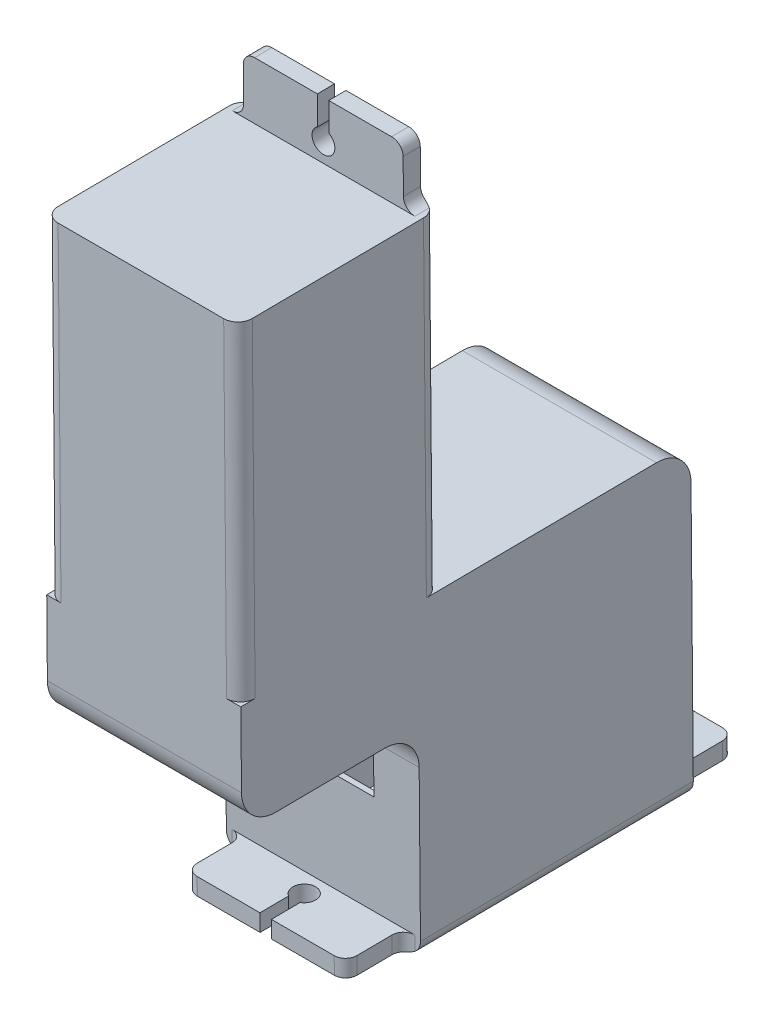
SolidWorks part; units mm, degrees
ref_plane "Front Plane" through (0, 0, 0) normal (0, 0, 1) x (1, 0, 0)
ref_plane "Top Plane" through (0, 0, 0) normal (0, 1, 0) x (1, 0, 0)
ref_plane "Right Plane" through (0, 0, 0) normal (1, 0, 0) x (0, 0, -1)
sketch "Sketch2" plane through (0, 48.5549, 0.4237) normal (0, 1, 0.0087) x (1, 0, 0)
  line L0 (-9.0464, 2.1053) -> (-9.0464, -2.2447) construction
  line L1 (-8.0464, -3.4447) -> (-22.0464, -3.4447)
  line L2 (-8.0464, -3.4447) -> (-8.0464, 2.1092)
  line L3 (-8.0464, 2.1092) -> (-22.0464, 2.1092)
  line L4 (-22.0464, -3.4447) -> (-22.0464, 2.1092)
  line L5 (-21.0464, -2.2447) -> (-21.0464, 2.1053) construction
  line L6 (-15.5464, -2.4447) -> (-20.8464, -2.4447) construction
  dimension "D1" = 1
  dimension "D2" = 1
  dimension "D3" = 1
extrude "Boss-Extrude1" add sketch "Sketch2" along normal blind 1.5
sketch "Sketch3" plane through (0, 48.5549, 0.4237) normal (0, -1, -0.0087) x (1, 0, 0)
  line L0 (-16.0464, 0.0697) -> (-14.0464, 0.0697) construction
  line L1 (-15.5464, 0.9358) -> (-15.5464, 3.4447)
  line L2 (-22.0464, 3.4447) -> (-8.0464, 3.4447) construction
  line L3 (-14.5464, 0.9358) -> (-14.5464, 2.4447)
  line L4 (-14.5464, 2.4447) -> (-14.5464, 3.4447)
  line L5 (-14.5464, 3.4447) -> (-15.5464, 3.4447)
  arc A0 (-15.5464, 0.9358) -> (-14.5464, 0.9358) centre (-15.0464, 0.0697) ccw construction
  circle A1 centre (-15.0464, 0.0697) radius 1
  line M2 (-8.0464, 3.4447) -> (-22.0464, 3.4447)
extrude "Cut-Extrude1" cut sketch "Sketch3" against normal up to next contours A1 L0 | A1 L3 L4 L1 M2
sketch "Sketch4" plane through (0, 50.0548, 0.4368) normal (0, 1, 0.0087) x (1, 0, 0)
  line L0 (-20.8464, 24.6053) -> (-20.8464, 2.5053) construction
  line L1 (-20.8464, 13.5553) -> (-23.5464, 13.5553)
  line L2 (-21.0464, 2.5053) -> (-21.0464, 24.6053) construction
  line L3 (-23.5464, 2.1092) -> (-23.5464, 13.5553)
  line L4 (-22.0464, -3.4447) -> (-23.1358, -3.4447)
  line L5 (-21.5464, 2.1092) -> (-21.5464, 13.5553)
  line L6 (-23.5464, 13.5553) -> (-23.5464, 15.5553)
  line L7 (-23.5464, 15.5553) -> (-21.5464, 15.5553)
  line L8 (-23.5464, 2.1092) -> (-23.5464, -3.4447)
  line L9 (-23.5464, -3.4447) -> (-23.1358, -3.4447)
  line L10 (-21.5464, 2.1092) -> (-22.0464, 2.1092)
  line L11 (-22.0464, 2.1092) -> (-22.0464, -3.4447)
  line L12 (-15.0464, 0.9303) -> (-15.0464, 3.2859)
  line L13 (-9.2464, 13.5553) -> (-6.5464, 13.5553)
  line L14 (-8.5464, 2.1092) -> (-8.5464, 13.5553)
  line L15 (-8.5464, 2.1092) -> (-8.0464, 2.1092)
  line L16 (-8.0464, 2.1092) -> (-8.0464, -3.4447)
  line L17 (-8.0464, -3.4447) -> (-6.957, -3.4447)
  line L18 (-6.5464, -3.4447) -> (-6.957, -3.4447)
  line L19 (-6.5464, 2.1092) -> (-6.5464, -3.4447)
  line L20 (-6.5464, 2.1092) -> (-6.5464, 13.5553)
  line L21 (-21.5464, 2.1092) -> (-21.5464, -3.4447)
  line L22 (-22.0464, -3.4447) -> (-15.5464, -3.4447) construction
  line L23 (-21.5464, -3.4447) -> (-22.0464, -3.4447)
  line L24 (-8.0464, -3.4447) -> (-8.5464, -3.4447)
  line L25 (-14.5464, -3.4447) -> (-8.0464, -3.4447) construction
  line L26 (-8.5464, -3.4447) -> (-8.5464, 2.1092)
  line L27 (-21.5464, 2.1092) -> (-8.5464, 2.1092)
  line L28 (-6.5464, 1.6092) -> (-23.5464, 1.6092)
  line L29 (-21.5464, 15.5553) -> (-21.5464, 13.5553)
  line L30 (-8.5464, 13.5553) -> (-8.5464, 15.5553)
  line L31 (-8.5464, 15.5553) -> (-6.5464, 15.5553)
  line L32 (-6.5464, 15.5553) -> (-6.5464, 13.5553)
  arc A0 (-14.5464, -0.9358) -> (-15.5464, -0.9358) centre (-15.0464, -0.0697) ccw construction
  line M13 (-8.0464, 2.1092) -> (-22.0464, 2.1092)
  line M14 (-22.0464, 2.1092) -> (-22.0464, -3.4447)
  dimension "D1" = 0.5
  dimension "D2" = 2
  dimension "D3" = 0.5
  dimension "D4" = 2
extrude "Boss-Extrude2" add sketch "Sketch4" along normal blind 16 and the other way up to surface contours L28 L12 L21 M13 | L28 L26 L12 M13 | L28 L16 L26 M13 | L28 L19 L20 L13 L14 L16 M13 | L28 L5 L1 L3 L8 M14 M13 | L28 L21 M13 M14
fillet "Fillet1" radius 1 4 edges at (-8.0464, 49.2748, 3.8749) (-22.0464, 49.2748, 3.8749) (-22.0464, 49.3189, -1.1788) (-8.0464, 49.3189, -1.1788)
sketch "Sketch5" plane through (0, 0.0184, -2.1091) normal (0, 0.0087, -1) x (-1, 0, 0)
  line L0 (21.5464, 48.5567) -> (21.5464, 66.0567) construction
  line L1 (8.5464, 66.0567) -> (21.5464, 66.0567)
  line L2 (8.5464, 66.0567) -> (8.5464, 64.7567)
  line L3 (8.5464, 64.7567) -> (21.5464, 64.7567)
  line L4 (21.5464, 66.0567) -> (21.5464, 64.7567)
  line L5 (9.2464, 64.5567) -> (20.8464, 64.5567) construction
  dimension "D1" = 0.2
extrude "Boss-Extrude3" add sketch "Sketch5" along normal up to surface (11.4461 mm away) up to face at (-7.5464, 57.4228, -13.0547)
fillet "Fillet2" radius 1.25 4 edges at (-6.5464, 48.621, -7.1582) (-6.5464, 66.1204, -7.0055) (-23.5464, 48.621, -7.1582) (-23.5464, 66.1204, -7.0055)
mirror "Mirror1" about plane through (0, 27.8963, -13.3123) normal (0, -0.0087, 1) of bodies 104
sketch "Sketch10" plane through (0, 0.014, -1.6091) normal (0, -0.0087, 1) x (1, 0, 0)
  line L0 (-15.0464, 66.0567) -> (-15.0464, 62.8067)
  line L1 (-7.7964, 66.0567) -> (-22.2964, 66.0567) construction
  line L3 (-15.0464, 62.8067) -> (-10.5464, 62.8067)
  line L4 (-10.5464, 62.8067) -> (-10.5464, 58.8067)
  line L5 (-10.5464, 58.8067) -> (-19.5464, 58.8067)
  line L6 (-19.5464, 58.8067) -> (-19.5464, 62.8067)
  line L7 (-19.5464, 62.8067) -> (-15.0464, 62.8067)
  dimension "D1" = 3.25
  dimension "D2" = 9
  dimension "D3" = 4.5
  dimension "D4" = 4
extrude "Cut-Extrude2" cut sketch "Sketch10" against normal blind 5 contours L7 L6 L5 L4 L3
sketch "Sketch11" plane through (-10.5464, 0, 0) normal (-1, 0, 0) x (0, 0, 1)
  line L0 (-1.0959, 58.8185) -> (-1.5959, 58.8229)
  line L1 (-1.5959, 58.8229) -> (-1.6892, 48.1333)
  line L2 (-1.6892, 48.1333) -> (-1.1892, 48.1333)
  line L3 (-1.1892, 48.1333) -> (-1.5959, 58.8229)
  dimension "D1" = 0.5
ref_plane "Plane2" through (0, -0.1173, 13.4442) normal (0, -0.0087, 1) x (1, 0, 0)
sketch "Sketch14" plane through (0, -0.1173, 13.4442) normal (0, -0.0087, 1) x (1, 0, 0)
  line L0 (-8.7473, 50.1358) -> (-14.839, 48.49)
  line L1 (-8.7473, 50.1358) -> (-6.5464, 52.3367)
  line L2 (-6.5464, 49.8067) -> (-6.5464, 64.8067) construction
  line L3 (-6.5464, 52.3367) -> (-6.5464, 71.0567)
  line L4 (-6.5464, 71.0567) -> (-16.7045, 71.0567)
  line L5 (-7.7964, 66.0567) -> (-22.2964, 66.0567) construction
  line L6 (-14.839, 48.49) -> (8.8302, 48.49)
  line L7 (0, 65.6042) -> (-11.5834, 65.6042)
  line L8 (0, 19.4955) -> (0, -19.4955) construction
  dimension "D1" = 5
pattern_circular "CirPattern1" count 2 over 360 about axis through (0, 65.4843, 14.0167) along (-1, 0, 0)
sketch "Sketch15" plane through (0, 66.0542, 0.5764) normal (0, 1, 0.0087) x (1, 0, 0)
  line L0 (-7.7964, 25.5014) -> (-7.7964, -15.9286)
  line L1 (-7.7964, -15.9286) -> (-22.2964, -15.9286)
  line L2 (-22.2964, -15.9286) -> (-22.2964, 25.5014)
  line L3 (-22.2964, 25.5014) -> (-7.7964, 25.5014)
extrude "Boss-Extrude4" add sketch "Sketch15" along normal up to surface (9.5475 mm away) up to face at (-18.2964, 75.6262, -2.1929)
sketch "Sketch16" plane through (0, 80.655, 0.7039) normal (0, -1, -0.0087) x (1, 0, 0)
  line L6 (-23.0464, -2.1027) -> (-21.8589, -2.1027)
  line L12 (-7.0464, -2.1027) -> (-7.0464, -3.3527)
  line L13 (-6.5464, -2.3527) -> (-6.5464, 12.6473)
  line L14 (-7.7964, 13.8973) -> (-22.2964, 13.8973)
  line L15 (-23.5464, 12.6473) -> (-23.5464, -2.3527)
  line L16 (-23.0464, -3.3527) -> (-23.0464, -2.1027)
  line L17 (-23.0464, -2.1027) -> (-7.0464, -2.1027)
  line L18 (-7.0464, -2.1027) -> (-7.0464, -3.3527)
  line L19 (-6.5464, -2.3527) -> (-6.5464, 12.6473)
  line L20 (-7.7964, 13.8973) -> (-22.2964, 13.8973)
  line L21 (-23.5464, 12.6473) -> (-23.5464, -2.3527)
  line L22 (-23.0464, -3.3527) -> (-23.0464, -2.1027)
  line L23 (-23.0464, -2.1027) -> (-7.0464, -2.1027)
  line L27 (-8.0464, -3.6027) -> (-7.7964, -3.6027)
  line L28 (-7.0464, -3.3527) -> (-7.0464, -2.1027)
  line L29 (-7.0464, -2.1027) -> (-8.0464, -2.1027)
  line L30 (-8.0464, -2.1027) -> (-8.0464, -3.6027)
  line L31 (-8.0464, -3.6027) -> (-7.7964, -3.6027)
  line L32 (-7.0464, -3.3527) -> (-7.0464, -2.1027)
  line L33 (-7.0464, -2.1027) -> (-8.0464, -2.1027)
  line L34 (-8.0464, -2.1027) -> (-8.0464, -3.6027)
  line L35 (-23.0464, -2.1027) -> (-22.0464, -2.1027)
  line L36 (-22.0464, -2.1027) -> (-22.0464, -3.6027)
  line L37 (-23.0464, -3.3527) -> (-23.0464, -2.1027)
  line L39 (-23.0464, -2.1027) -> (-23.0464, -3.3527)
  line L40 (-22.2964, -3.6027) -> (-22.0464, -3.6027)
  line L41 (-22.0464, -3.6027) -> (-22.0464, -2.1027)
  line L42 (-22.0464, -2.1027) -> (-23.0464, -2.1027)
  line L43 (-23.0464, -2.1027) -> (-23.0464, -3.3527)
  line L44 (-22.2964, -3.6027) -> (-22.0464, -3.6027)
  line L45 (-22.0464, -3.6027) -> (-22.0464, -2.1027)
  line L46 (-22.0464, -2.1027) -> (-23.0464, -2.1027)
  arc A6 (-7.7964, -3.6027) -> (-7.0464, -3.3527) centre (-7.7964, -2.3527) ccw
  arc A7 (-7.7964, -3.6027) -> (-7.0464, -3.3527) centre (-7.7964, -2.3527) ccw
  arc A8 (-7.0464, -3.3527) -> (-6.5464, -2.3527) centre (-7.7964, -2.3527) ccw
  arc A9 (-6.5464, 12.6473) -> (-7.7964, 13.8973) centre (-7.7964, 12.6473) ccw
  arc A10 (-22.2964, 13.8973) -> (-23.5464, 12.6473) centre (-22.2964, 12.6473) ccw
  arc A11 (-23.5464, -2.3527) -> (-23.0464, -3.3527) centre (-22.2964, -2.3527) ccw
  arc A12 (-7.0464, -3.3527) -> (-6.5464, -2.3527) centre (-7.7964, -2.3527) ccw
  arc A13 (-6.5464, 12.6473) -> (-7.7964, 13.8973) centre (-7.7964, 12.6473) ccw
  arc A14 (-22.2964, 13.8973) -> (-23.5464, 12.6473) centre (-22.2964, 12.6473) ccw
  arc A15 (-23.5464, -2.3527) -> (-23.0464, -3.3527) centre (-22.2964, -2.3527) ccw
  arc A16 (-22.0464, -3.6027) -> (-23.0464, -3.3527) centre (-22.0464, -1.4777) cw
  arc A17 (-23.0464, -3.3527) -> (-22.2964, -3.6027) centre (-22.2964, -2.3527) ccw
  arc A18 (-23.0464, -3.3527) -> (-22.2964, -3.6027) centre (-22.2964, -2.3527) ccw
  line M11 (-7.0464, -2.1027) -> (-7.0464, -3.3527)
  arc M12 (-7.0464, -3.3527) -> (-6.5464, -2.3527) centre (-7.7964, -2.3527) ccw
  line M13 (-6.5464, -2.3527) -> (-6.5464, 12.6473)
  arc M14 (-6.5464, 12.6473) -> (-7.7964, 13.8973) centre (-7.7964, 12.6473) ccw
  line M15 (-7.7964, 13.8973) -> (-22.2964, 13.8973)
  arc M16 (-22.2964, 13.8973) -> (-23.5464, 12.6473) centre (-22.2964, 12.6473) ccw
  line M17 (-23.5464, 12.6473) -> (-23.5464, -2.3527)
  arc M18 (-23.5464, -2.3527) -> (-23.0464, -3.3527) centre (-22.2964, -2.3527) ccw
  line M19 (-23.0464, -3.3527) -> (-23.0464, -2.1027)
  line M20 (-23.0464, -2.1027) -> (-7.0464, -2.1027)
  line M21 (-19.5464, 10.6473) -> (-10.5464, 10.6473)
  line M22 (-10.5464, 10.6473) -> (-10.5464, 6.6473)
  line M23 (-10.5464, 6.6473) -> (-19.5464, 6.6473)
  line M24 (-19.5464, 6.6473) -> (-19.5464, 10.6473)
  dimension "D1" = 0
  dimension "D2" = 0
  dimension "D3" = 0
sketch "Sketch19" plane through (0, 80.655, 0.7039) normal (0, -1, -0.0087) x (1, 0, 0)
  line L6 (-7.0464, -2.1027) -> (-8.0464, -2.1027)
  line L7 (-8.0464, -2.1027) -> (-8.0464, -3.6027)
  line L12 (-7.0464, -2.1027) -> (-7.0464, -3.3527)
  line L13 (-6.5464, -2.3527) -> (-6.5464, 12.6473)
  line L14 (-7.7964, 13.8973) -> (-22.2964, 13.8973)
  line L15 (-23.5464, 12.6473) -> (-23.5464, -2.3527)
  line L16 (-23.0464, -3.3527) -> (-23.0464, -2.1027)
  line L17 (-23.0464, -2.1027) -> (-7.0464, -2.1027)
  line L18 (-7.0464, -2.1027) -> (-7.0464, -3.3527)
  line L19 (-6.5464, -2.3527) -> (-6.5464, 12.6473)
  line L20 (-7.7964, 13.8973) -> (-22.2964, 13.8973)
  line L21 (-23.5464, 12.6473) -> (-23.5464, -2.3527)
  line L22 (-23.0464, -3.3527) -> (-23.0464, -2.1027)
  line L23 (-23.0464, -2.1027) -> (-7.0464, -2.1027)
  arc A4 (-8.0464, -3.6027) -> (-7.0464, -3.3527) centre (-8.0464, -1.4777) ccw
  arc A8 (-7.0464, -3.3527) -> (-6.5464, -2.3527) centre (-7.7964, -2.3527) ccw
  arc A9 (-6.5464, 12.6473) -> (-7.7964, 13.8973) centre (-7.7964, 12.6473) ccw
  arc A10 (-22.2964, 13.8973) -> (-23.5464, 12.6473) centre (-22.2964, 12.6473) ccw
  arc A11 (-23.5464, -2.3527) -> (-23.0464, -3.3527) centre (-22.2964, -2.3527) ccw
  arc A12 (-7.0464, -3.3527) -> (-6.5464, -2.3527) centre (-7.7964, -2.3527) ccw
  arc A13 (-6.5464, 12.6473) -> (-7.7964, 13.8973) centre (-7.7964, 12.6473) ccw
  arc A14 (-22.2964, 13.8973) -> (-23.5464, 12.6473) centre (-22.2964, 12.6473) ccw
  arc A15 (-23.5464, -2.3527) -> (-23.0464, -3.3527) centre (-22.2964, -2.3527) ccw
  point P9 (0, 0)
  dimension "D1" = 0
extrude "Boss-Extrude6" add sketch "Sketch16" along normal up to surface (5.0539 mm away) contours A16 L36 M20 M19 | L23 M20 M11 M12 M13 M14 M15 M16 M17 M18 M19 M24 M21 M22 M23 | L31 A7 L23 L34 M11
fillet "Fillet3" radius 1 2 edges at (-7.7964, 75.5564, 5.8068) (-22.2964, 75.5563, 5.8142)
sketch "Sketch20" plane through (0, 75.6013, 0.6598) normal (0, 1, 0.0087) x (1, 0, 0)
  line L8 (-7.7964, -15.9286) -> (-7.7964, -13.8973)
  line L9 (-7.7964, -13.8973) -> (-22.2964, -13.8973)
  line L10 (-22.2964, -13.8973) -> (-22.2964, -15.9286)
  line L11 (-22.2964, -15.9286) -> (-7.7964, -15.9286)
  line L12 (-7.7964, -15.9286) -> (-7.7964, -13.8973)
  line L13 (-7.7964, -13.8973) -> (-22.2964, -13.8973)
  line L14 (-22.2964, -13.8973) -> (-22.2964, -15.9286)
  line L15 (-22.2964, -15.9286) -> (-7.7964, -15.9286)
  dimension "D1" = 0
extrude "Cut-Extrude5" cut sketch "Sketch20" against normal up to surface (9.5475 mm away) up to face at (-15.0464, 65.9917, 7.7359)
fillet "Fillet4" radius 3 3 edges at (-15.0464, 65.9329, 14.4732) (-15.0464, 75.8238, -24.8406) (-15.0464, 66.0682, -1.0327)
sketch "Sketch21" plane through (0, 81.155, 0.7082) normal (0, 1, 0.0087) x (1, 0, 0)
  line L0 (-10.5464, -6.6473) -> (-10.5464, -10.6473)
  line L1 (-10.5464, -10.6473) -> (-19.5464, -10.6473)
  line L2 (-19.5464, -10.6473) -> (-19.5464, -6.6473)
  line L3 (-19.5464, -6.6473) -> (-10.5464, -6.6473)
extrude "Cut-Extrude6" cut sketch "Sketch21" against normal up to surface (15.1014 mm away) up to face at (-15.0464, 66.0006, 6.7203)
sketch "Sketch23" plane through (0, 0.0314, -3.6026) normal (0, 0.0087, -1) x (-1, 0, 0)
  line L0 (9.2001, 75.6042) -> (8.0464, 75.6042)
  line L1 (14.5464, 75.6042) -> (9.0464, 75.6042) construction
  line L2 (8.0464, 75.6042) -> (8.0464, 76.6042) construction
  line L3 (8.0464, 75.6042) -> (8.0464, 76.6487)
  line L4 (8.0464, 76.6487) -> (9.2001, 75.6042)
  line L5 (20.8711, 75.6042) -> (22.0464, 75.6042)
  line L6 (21.0464, 75.6042) -> (15.5464, 75.6042) construction
  line L7 (22.0464, 75.6042) -> (22.0464, 76.9283)
  line L8 (22.0464, 79.6581) -> (22.0464, 76.6042) construction
  line L9 (22.0464, 76.9283) -> (20.8711, 75.6042)
extrude "Boss-Extrude7" add sketch "Sketch23" against normal up to surface (17.5 mm away) up to face at (-15.0464, 82.6126, 14.6188)
sketch "Sketch24" plane through (0, 0.0183, -2.1026) normal (0, 0.0087, -1) x (-1, 0, 0)
  circle A0 centre (15.0464, 78.9792) radius 1.0028
extrude "Cut-Extrude7" cut sketch "Sketch24" against normal blind 6
sketch "Sketch25" plane through (-22.2964, 0, 0) normal (-1, 0, 0) x (0, 0, 1)
  line L8 (-2.9281, 75.6326) -> (14.5565, 75.48)
  line L9 (14.8091, 104.425) -> (14.5478, 74.48) construction
  line L10 (14.5565, 75.48) -> (14.5478, 74.48)
  line L11 (-1.0589, 63.0683) -> (-24.9501, 63.2768)
  line L12 (-25.0657, 50.0273) -> (-24.9348, 65.0268) construction
  line L13 (-24.9501, 63.2768) -> (-24.8668, 72.8239)
  line L14 (14.5565, 75.48) -> (-2.9281, 75.6326)
  line L16 (-2.9281, 75.6326) -> (-21.8407, 75.7976)
  line L17 (-24.8668, 72.8239) -> (-24.9239, 66.2767)
  line L18 (-24.9239, 66.2767) -> (-1.0327, 66.0682)
  line L19 (-1.0327, 66.0682) -> (-1.0589, 63.0683)
  line L20 (1.9672, 66.0421) -> (11.4733, 65.9591)
  line L21 (14.4994, 68.9328) -> (14.5478, 74.48)
  line L22 (14.5478, 74.48) -> (-2.9368, 74.6326)
  line L23 (-2.9368, 74.6326) -> (-2.9281, 75.6326)
  line L24 (-2.9281, 75.6326) -> (-21.8407, 75.7976)
  line L25 (-24.8668, 72.8239) -> (-24.9239, 66.2767)
  line L26 (-24.9239, 66.2767) -> (-1.0327, 66.0682)
  line L27 (-1.0327, 66.0682) -> (-1.0589, 63.0683)
  line L28 (1.9672, 66.0421) -> (11.4733, 65.9591)
  line L29 (14.4994, 68.9328) -> (14.5478, 74.48)
  line L30 (14.5478, 74.48) -> (-2.9368, 74.6326)
  line L31 (-2.9368, 74.6326) -> (-2.9281, 75.6326)
  arc A6 (-21.8407, 75.7976) -> (-24.8668, 72.8239) centre (-21.8669, 72.7978) ccw
  arc A7 (1.9672, 66.0421) -> (-1.0589, 63.0683) centre (1.941, 63.0422) ccw
  arc A8 (11.4733, 65.9591) -> (14.4994, 68.9328) centre (11.4995, 68.959) ccw
  arc A9 (-21.8407, 75.7976) -> (-24.8668, 72.8239) centre (-21.8669, 72.7978) ccw
  arc A10 (1.9672, 66.0421) -> (-1.0589, 63.0683) centre (1.941, 63.0422) ccw
  arc A11 (11.4733, 65.9591) -> (14.4994, 68.9328) centre (11.4995, 68.959) ccw
  line M12 (-2.9281, 75.6326) -> (-21.8407, 75.7976)
  arc M13 (-21.8407, 75.7976) -> (-24.8668, 72.8239) centre (-21.8669, 72.7978) ccw
  line M14 (-24.8668, 72.8239) -> (-24.9239, 66.2767)
  line M15 (-24.9239, 66.2767) -> (-1.0327, 66.0682)
  line M16 (-1.0327, 66.0682) -> (-1.0589, 63.0683)
  arc M17 (-1.0589, 63.0683) -> (1.9672, 66.0421) centre (1.941, 63.0422) cw
  line M18 (1.9672, 66.0421) -> (11.4733, 65.9591)
  arc M19 (11.4733, 65.9591) -> (14.4994, 68.9328) centre (11.4995, 68.959) ccw
  line M20 (14.4994, 68.9328) -> (14.5478, 74.48)
  line M21 (14.5478, 74.48) -> (-2.9368, 74.6326)
  line M22 (-2.9368, 74.6326) -> (-2.9281, 75.6326)
  dimension "D1" = 0
extrude "Boss-Extrude8" add sketch "Sketch25" along normal up to surface (1.25 mm away) contours M22 M12 M13 M14 M15 M16 M17 M18 M19 M20 M21 | L13 L11 M16 M15 | L10 L8 M22 M21 up to face at (-23.5464, 57.4228, -13.0547)
sketch "Sketch26" plane through (-7.7964, 0, 0) normal (1, 0, 0) x (0, 0, -1)
  line L8 (2.9428, 75.6327) -> (-14.5565, 75.48)
  line L9 (-14.5565, 75.48) -> (-14.5478, 74.48)
  line L10 (1.0589, 63.0683) -> (24.9519, 63.0683)
  line L11 (25.0657, 50.0273) -> (24.9348, 65.0268) construction
  line L12 (24.9519, 63.0683) -> (24.9239, 66.2767)
  line L16 (24.9239, 66.2767) -> (24.8668, 72.8239)
  line L17 (21.8407, 75.7976) -> (2.9428, 75.6327)
  line L18 (2.9428, 75.6327) -> (2.9516, 74.6328)
  line L19 (2.9516, 74.6328) -> (-14.5478, 74.48)
  line L20 (-14.5478, 74.48) -> (-14.4994, 68.9328)
  line L21 (-11.4733, 65.9591) -> (-1.9672, 66.0421)
  line L22 (1.0589, 63.0683) -> (1.0327, 66.0682)
  line L23 (1.0327, 66.0682) -> (24.9239, 66.2767)
  line L24 (24.9239, 66.2767) -> (24.8668, 72.8239)
  line L25 (21.8407, 75.7976) -> (2.9428, 75.6327)
  line L26 (2.9428, 75.6327) -> (2.9516, 74.6328)
  line L27 (2.9516, 74.6328) -> (-14.5478, 74.48)
  line L28 (-14.5478, 74.48) -> (-14.4994, 68.9328)
  line L29 (-11.4733, 65.9591) -> (-1.9672, 66.0421)
  line L30 (1.0589, 63.0683) -> (1.0327, 66.0682)
  line L31 (1.0327, 66.0682) -> (24.9239, 66.2767)
  arc A6 (24.8668, 72.8239) -> (21.8407, 75.7976) centre (21.8669, 72.7978) ccw
  arc A7 (-14.4994, 68.9328) -> (-11.4733, 65.9591) centre (-11.4995, 68.959) ccw
  arc A8 (1.0589, 63.0683) -> (-1.9672, 66.0421) centre (-1.941, 63.0422) ccw
  arc A9 (24.8668, 72.8239) -> (21.8407, 75.7976) centre (21.8669, 72.7978) ccw
  arc A10 (-14.4994, 68.9328) -> (-11.4733, 65.9591) centre (-11.4995, 68.959) ccw
  arc A11 (1.0589, 63.0683) -> (-1.9672, 66.0421) centre (-1.941, 63.0422) ccw
  line M12 (24.9239, 66.2767) -> (24.8668, 72.8239)
  arc M13 (24.8668, 72.8239) -> (21.8407, 75.7976) centre (21.8669, 72.7978) ccw
  line M14 (21.8407, 75.7976) -> (2.9428, 75.6327)
  line M15 (2.9428, 75.6327) -> (2.9516, 74.6328)
  line M16 (2.9516, 74.6328) -> (-14.5478, 74.48)
  line M17 (-14.5478, 74.48) -> (-14.4994, 68.9328)
  arc M18 (-14.4994, 68.9328) -> (-11.4733, 65.9591) centre (-11.4995, 68.959) ccw
  line M19 (-11.4733, 65.9591) -> (-1.9672, 66.0421)
  arc M20 (-1.9672, 66.0421) -> (1.0589, 63.0683) centre (-1.941, 63.0422) cw
  line M21 (1.0589, 63.0683) -> (1.0327, 66.0682)
  line M22 (1.0327, 66.0682) -> (24.9239, 66.2767)
  dimension "D1" = 0
extrude "Boss-Extrude9" add sketch "Sketch26" along normal up to surface (1.25 mm away) contours M22 M12 M13 M14 M15 M16 M17 M18 M19 M20 M21 | L8 L9 M16 M15 | L10 L12 M22 M21 up to face at (-6.5464, 57.4228, -13.0547)
sketch "Sketch28" plane through (0, 48.5549, 0.4237) normal (0, -1, -0.0087) x (1, 0, 0)
  line L0 (-21.5464, -2.1092) -> (-21.5464, -1.3092)
  line L1 (-21.5464, -2.1092) -> (-21.5464, -25.0014) construction
  line L2 (-8.5464, -2.1092) -> (-8.5464, -1.3092)
  line L3 (-21.5464, -1.3092) -> (-8.5464, -1.3092)
  line L4 (-21.5464, -25.0014) -> (-21.5464, -13.5553) construction
  line L5 (-21.5464, -13.5553) -> (7.3721, -13.5553) construction
  line L6 (-21.5464, -2.1092) -> (-8.5464, -2.1092)
  line L7 (-21.5464, -25.0014) -> (-21.5464, -25.8014)
  line L8 (-21.5464, -25.8014) -> (-8.5464, -25.8014)
  line L9 (-8.5464, -25.0014) -> (-8.5464, -25.8014)
  line L10 (-21.5464, -25.0014) -> (-8.5464, -25.0014)
  dimension "D1" = 0.8
